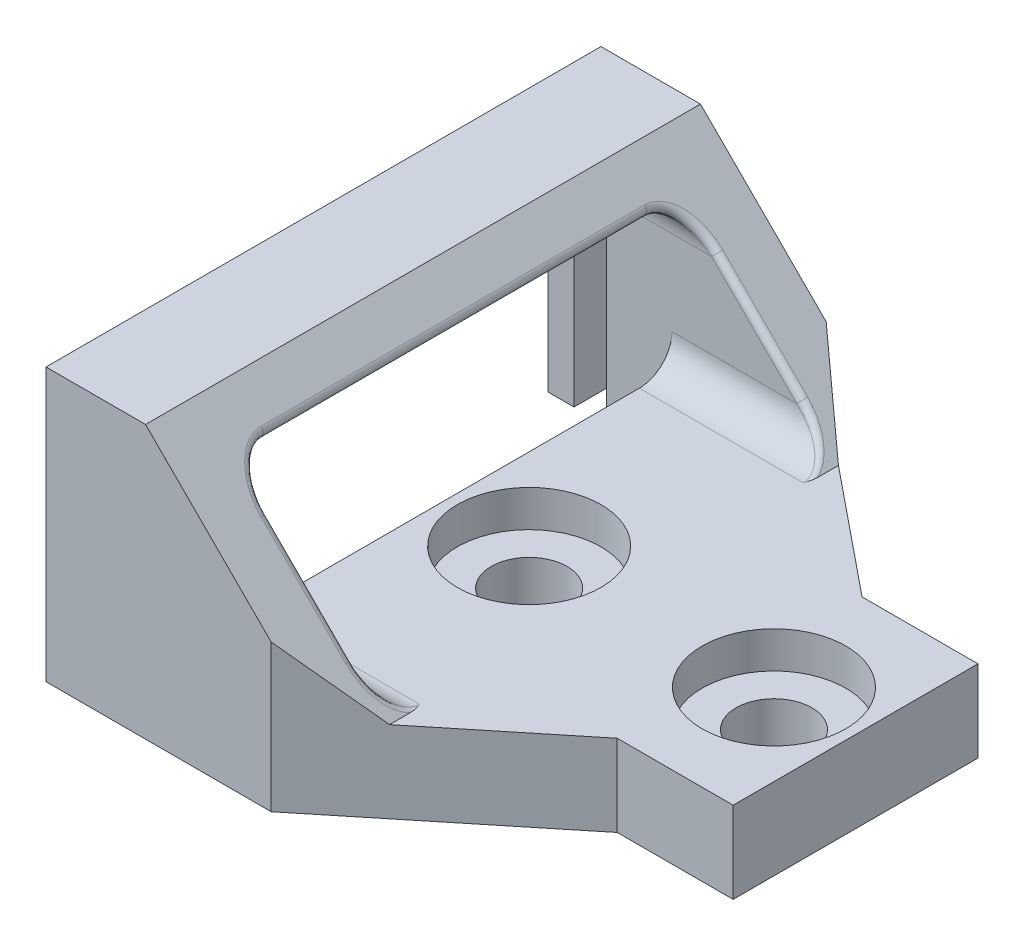
SolidWorks part; units mm, degrees
ref_plane "Front Plane" through (0, 0, 0) normal (0, 0, 1) x (1, 0, 0)
ref_plane "Top Plane" through (0, 0, 0) normal (0, 1, 0) x (1, 0, 0)
ref_plane "Right Plane" through (0, 0, 0) normal (1, 0, 0) x (0, 0, -1)
sketch "Sketch1" plane through (0, 0, 0) normal (0, 1, 0) x (1, 0, 0)
  line L0 (0, 8.7312) -> (0, 10.16)
  line L1 (0, 10.16) -> (-1.27, 10.16)
  line L2 (-1.27, 10.16) -> (-1.27, 8.7312)
  line L3 (-1.27, 8.7312) -> (-2.286, 8.7312)
  line L4 (-2.286, 8.7312) -> (-2.286, 11.7475)
  line L5 (-2.286, 11.7475) -> (1.5875, 11.7475)
  line L6 (0, 8.7312) -> (1.5875, 8.7312)
  line L7 (0, 0) -> (4.6182, 0) construction
  line L8 (1.5875, 11.7475) -> (1.5875, 8.7312)
  dimension "D1" = 1.016
  dimension "D2" = 20.32
  dimension "D3" = 1.27
  dimension "D4" = 1.5875
  dimension "D5" = 17.4625
  dimension "D6" = 1.5875
extrude "Boss-Extrude1" add sketch "Sketch1" along normal blind 9.017
sketch "Sketch2" plane through (0, 0, 0) normal (0, 1, 0) x (1, 0, 0)
  line L0 (0, 0) -> (25.0773, 0) construction
  line L1 (18.415, -11.7475) -> (18.415, 11.7475)
  line L3 (1.5875, 8.7312) -> (1.5875, 11.7475)
  line L4 (1.5875, -8.7312) -> (2.54, -8.7312)
  line L5 (1.5875, 8.7312) -> (1.5875, 11.7475) construction
  line L8 (2.54, 8.7312) -> (2.54, -8.7312)
  line L11 (1.5875, 11.7475) -> (18.415, 11.7475)
  line L12 (1.5875, -8.7312) -> (1.5875, -11.7475)
  line L13 (1.5875, -11.7475) -> (18.415, -11.7475)
  line L15 (0, 10.16) -> (0, 8.7312) construction
  line L16 (1.5875, 8.7312) -> (2.54, 8.7312)
  circle A0 centre (5.715, 0) radius 1.4732 construction
  circle A1 centre (15.24, 0) radius 1.4732 construction
  circle A2 centre (15.24, 0) radius 2.794 construction
  circle A3 centre (5.715, 0) radius 2.794 construction
  point P12 (2.54, 0)
  point P21 (18.415, 0)
  dimension "D1" = 2.9464
  dimension "D3" = 5.588
  dimension "D2" = 9.525
  dimension "D4" = 3.175
  dimension "D5" = 3.175
  dimension "D6" = 2.54
extrude "Boss-Extrude2" add sketch "Sketch2" along normal blind 3.175
mirror "Mirror2" about plane through (0, 0, 0) normal (0, 0, 1) of "Boss-Extrude1"
sketch "Sketch9" plane through (0, 9.017, 0) normal (0, 1, 0) x (1, 0, 0)
  line L1 (-2.286, 11.7475) -> (1.5875, 11.7475)
  line L2 (-2.286, 11.7475) -> (-2.286, -11.7475)
  line L3 (-2.286, -11.7475) -> (1.5875, -11.7475)
  line L4 (1.5875, 11.7475) -> (1.5875, -11.7475)
extrude "Boss-Extrude6" add sketch "Sketch9" along normal blind 1.5875
sketch "Sketch7" plane through (0, 0, -11.7475) normal (0, 0, -1) x (-1, 0, 0)
  line L0 (-1.5875, 10.6045) -> (-9.017, 3.175)
  line L1 (-18.415, 3.175) -> (-1.5875, 3.175) construction
  line L2 (-9.017, 3.175) -> (-1.5875, 3.175)
  line L3 (-1.5875, 3.175) -> (-1.5875, 10.6045)
extrude "Boss-Extrude10" add sketch "Sketch7" against normal up to surface (23.495 mm away) up to face at (5.9055, 4.5932, 11.7475)
sketch "Sketch11" plane through (1.5875, 0, 0) normal (-1, 0, 0) x (0, 0, 1)
  line L4 (-8.7312, 9.017) -> (-8.7312, 3.175)
  line L5 (-8.7312, 3.175) -> (8.7312, 3.175)
  line L6 (8.7312, 3.175) -> (8.7312, 9.017)
  line L7 (8.7312, 9.017) -> (-8.7312, 9.017)
  line L8 (-8.7312, 9.017) -> (-8.7312, 3.175)
  line L9 (-8.7312, 3.175) -> (8.7312, 3.175)
  line L10 (8.7312, 3.175) -> (8.7312, 9.017)
  line L11 (8.7312, 9.017) -> (-8.7312, 9.017)
  dimension "D1" = 0
extrude "Cut-Extrude3" cut sketch "Sketch11" against normal up to next
sketch "Sketch12" plane through (0, 0, 0) normal (0, 1, 0) x (1, 0, 0)
  line L0 (18.415, 4.7625) -> (13.9048, 4.7625)
  line L1 (18.415, -11.7475) -> (18.415, 11.7475) construction
  line L2 (13.9048, 4.7625) -> (5.3022, 11.7475)
  line L3 (1.5875, 11.7475) -> (9.017, 11.7475) construction
  line L4 (0, 0) -> (18.415, 0) construction
  line L5 (5.3022, 11.7475) -> (18.415, 11.7475)
  line L6 (18.415, 11.7475) -> (18.415, 4.7625)
  dimension "D1" = 9.525
extrude "Cut-Extrude4" cut sketch "Sketch12" along normal up to next
mirror "Mirror8" about plane through (0, 0, 0) normal (0, 0, 1) of "Cut-Extrude4"
hole_wizard "CBORE for #4 Button Head Cap Screw1" positions "Sketch14" profile "Sketch13" counterbore size "#4" standard "ANSI Inch" end condition through all
sketch "Sketch14" plane through (0, 3.175, 0) normal (0, 1, 0) x (1, 0, 0)
  point P0 (15.24, 0)
  point P2 (5.715, 0)
sketch "Sketch13" plane through (15.24, 3.175, 0) normal (1, 0, 0) x (0, 0, 1)
  line L0 (0, 0) -> (0, 3.175)
  line L1 (0, 3.175) -> (1.4732, 3.175)
  line L3 (1.4732, 3.175) -> (1.4732, 1.4224)
  line L4 (1.4732, 1.4224) -> (2.794, 1.4224)
  line L5 (2.794, 1.4224) -> (2.794, 0)
  line L7 (2.794, 0) -> (0, 0)
  line L11 (0, -6.35) -> (0, 107.95) construction
  dimension "Thru Hole Dia." = 2.9464
  dimension "Thru Hole Depth" = 3.175
  dimension "C'Bore Dia." = 5.588
  dimension "C'Bore Depth" = 1.4224
fillet "Fillet3" radius 1.27 4 edges at (5.7785, 3.175, 8.7312) (5.7785, 3.175, -8.7312)
sketch "Sketch15" plane through (0, 10.6045, 0) normal (0, 1, 0) x (1, 0, 0)
  line L0 (0, 0) -> (27.4333, 0) construction
  line L1 (-2.286, 10.795) -> (6.4753, 10.795)
  line L2 (-2.286, 11.7475) -> (-2.286, -11.7475) construction
  line L3 (5.3023, 11.7475) -> (9.017, 8.7312) construction
  line L4 (6.4753, 10.795) -> (5.3023, 11.7475)
  line L5 (5.3023, 11.7475) -> (-2.286, 11.7475)
  line L6 (-2.286, 11.7475) -> (-2.286, 10.795)
  line L7 (-2.286, -11.7475) -> (-2.286, -10.795)
  line L8 (5.3023, -11.7475) -> (-2.286, -11.7475)
  line L9 (6.4753, -10.795) -> (5.3023, -11.7475)
  line L10 (-2.286, -10.795) -> (6.4753, -10.795)
  dimension "D1" = 21.59
extrude "Cut-Extrude5" cut sketch "Sketch15" against normal through all
fillet "Fillet4" radius 0.254 7 edges at (8.645, 3.547, 8.3593) (6.096, 6.096, 8.7312) (3.547, 8.645, 8.3593) (8.645, 3.547, -8.3593) (6.096, 6.096, -8.7312) (3.547, 8.645, -8.3593) (3.175, 9.017, 0)
